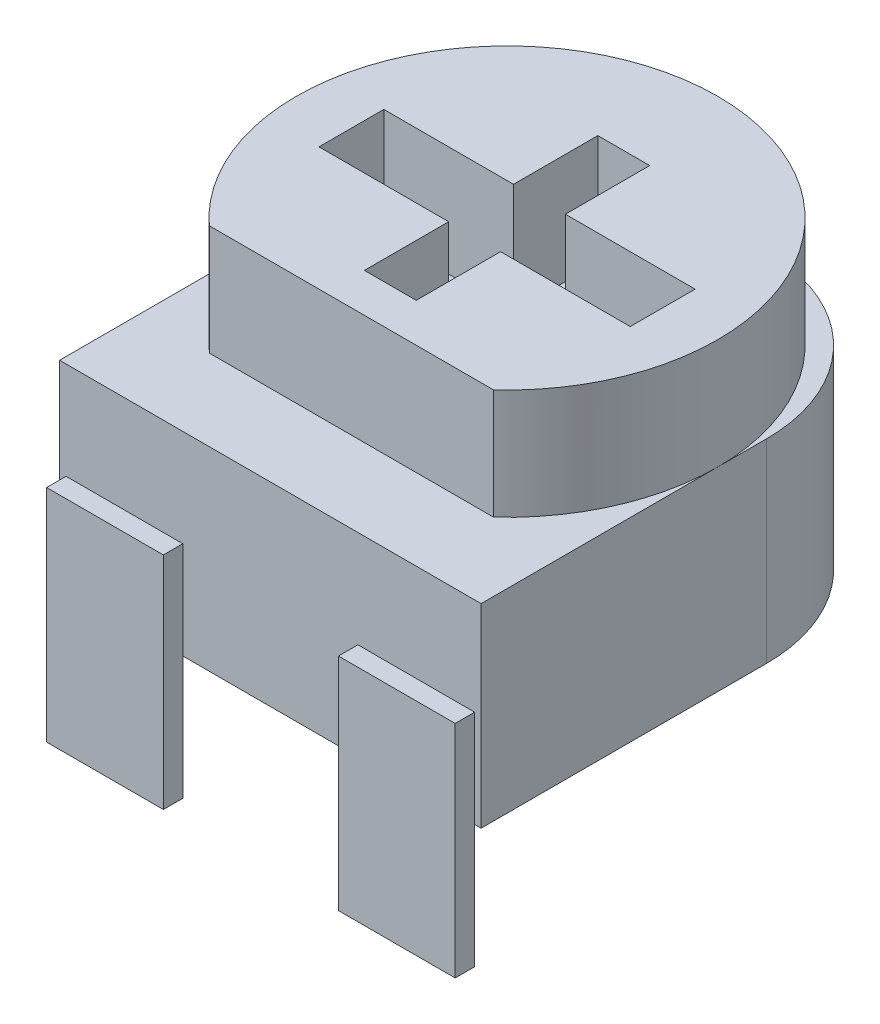
SolidWorks part; units mm, degrees
note: The reader was unsure of these and kept them because the rebuilt part matched: shared geometry of "草图1<3>", "草图1<4>".
ref_plane "前视基准面" through (0, 0, 0) normal (0, 0, 1) x (1, 0, 0)
ref_plane "上视基准面" through (0, 0, 0) normal (0, 1, 0) x (1, 0, 0)
ref_plane "右视基准面" through (0, 0, 0) normal (1, 0, 0) x (0, 0, -1)
other "Configuration Table"
sketch "草图1" plane through (0, 0, 0) normal (0, 1, 0) x (1, 0, 0)
  line L0 (-2.1915, -2.4) -> (2.1915, -2.4)
  line L1 (-3.25, 3.25) -> (3.25, 3.25)
  line L2 (-3.25, 3.25) -> (-3.25, -3.65)
  line L3 (-3.25, -3.65) -> (3.25, -3.65)
  line L4 (3.25, 3.25) -> (3.25, -3.65)
  line L5 (0, 3.25) -> (0, -3.65) construction
  line L6 (-2.4, -0.5) -> (2.4, -0.5)
  line L7 (-2.4, -0.5) -> (-2.4, 0.5)
  line L8 (-2.4, 0.5) -> (2.4, 0.5)
  line L9 (2.4, -0.5) -> (2.4, 0.5)
  line L10 (-2.4, -0.5) -> (2.4, 0.5) construction
  line L11 (-2.4, 0.5) -> (2.4, -0.5) construction
  line L12 (-0.4, -1.8) -> (0.4, -1.8)
  line L13 (-0.4, -1.8) -> (-0.4, 1.8)
  line L14 (-0.4, 1.8) -> (0.4, 1.8)
  line L15 (0.4, -1.8) -> (0.4, 1.8)
  line L16 (-0.4, -1.8) -> (0.4, 1.8) construction
  line L17 (-0.4, 1.8) -> (0.4, -1.8) construction
  circle A0 centre (0, 0) radius 3.25
  circle A1 centre (0, 0) radius 1.8
  point P20 (0, 0)
  point P21 (0, 0)
  dimension "D4" = 1.25
  dimension "D1" = 3.25
  dimension "D2" = 3.65
  dimension "D3" = 6.5
  dimension "D5" = 0.8
  dimension "D6" = 1
  dimension "D7" = 4.8
  dimension "D8" = 3.6
extrude "凸台-拉伸1" add sketch "草图1" along normal blind 3 contours L4 L3 L2 L1
extrude "凸台-拉伸2" add sketch "草图1<3>" along normal blind 1.7 from surface at 3 contours A0 | L6 L9 L8 L7 | L13 L14 L15 L12
sketch "草图1<3>" plane through (0, 0, 0) normal (0, 1, 0) x (1, 0, 0) same geometry as "草图1"
extrude "切除-拉伸1" cut sketch "草图1<4>" against normal up to surface (1.7 mm away) from surface at 4.7 contours L0 A0 up to face at (0, 3, 2.6375) starting at face at (0, 4.7, -3.25)
sketch "草图1<4>" plane through (0, 0, 0) normal (0, 1, 0) x (1, 0, 0) same geometry as "草图1"
fillet "圆角1" radius 2.5 2 edges at (3.25, 1.5, -3.25) (-3.25, 1.5, -3.25)
sketch "草图2" plane through (0, 0, 3.65) normal (0, 0, 1) x (1, 0, 0)
  line L0 (-3.25, 1.5) -> (3.25, 1.5)
  line L1 (-3.25, 3) -> (-3.25, 0) construction
  line L2 (3.25, 3) -> (3.25, 0) construction
  line L4 (-3.15, 1.5) -> (-1.35, 1.5)
  line L5 (-3.15, 1.5) -> (-3.15, -1.9)
  line L6 (-3.15, -1.9) -> (-1.35, -1.9)
  line L7 (-1.35, 1.5) -> (-1.35, -1.9)
  line L8 (1.35, 1.5) -> (3.15, 1.5)
  line L9 (1.35, 1.5) -> (1.35, -1.9)
  line L10 (1.35, -1.9) -> (3.15, -1.9)
  line L11 (3.15, 1.5) -> (3.15, -1.9)
  dimension "D1" = 0.1
  dimension "D2" = 0.1
  dimension "D3" = 1.8
  dimension "D4" = 1.8
  dimension "D5" = 3.4
  dimension "D6" = 3.4
extrude "凸台-拉伸3" add sketch "草图2" along normal blind 0.3 contours L5 L6 L7 L4 | L9 L10 L11 L8
sketch "草图3" plane through (0, 0, 0) normal (0, -1, 0) x (1, 0, 0)
  line L0 (0, 0) -> (0, -2.25)
  line L1 (-1.15, -2.25) -> (1.15, -2.25)
  line L2 (-1.15, -2.25) -> (-1.15, -2.55)
  line L3 (-1.15, -2.55) -> (1.15, -2.55)
  line L4 (1.15, -2.25) -> (1.15, -2.55)
  line L5 (-0.75, -3.25) -> (0.75, -3.25) construction
  dimension "D1" = 0.7
  dimension "D2" = 0.3
  dimension "D3" = 2.3
extrude "凸台-拉伸4" add sketch "草图3" along normal up to surface (1.9 mm away) contours L1 L4 L3 L2 up to face at (2.25, -1.9, 3.8)
